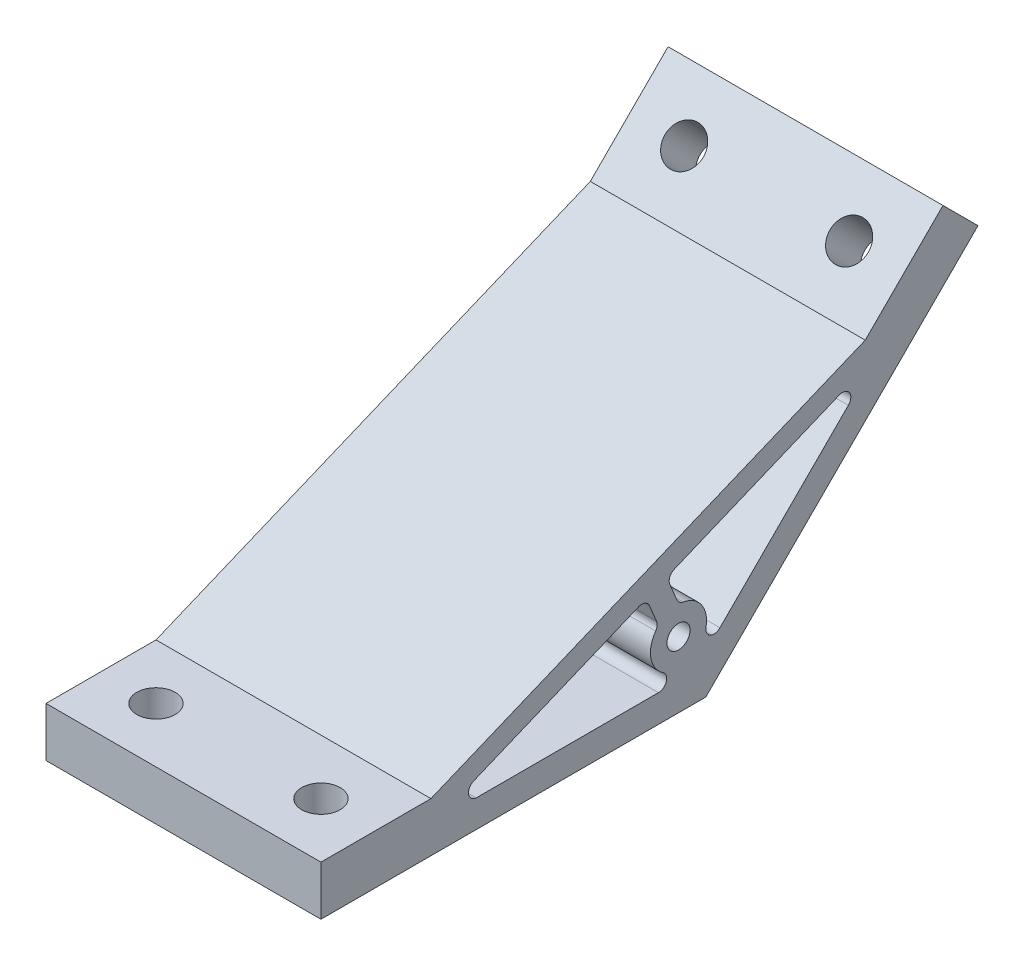
SolidWorks part; units mm, degrees
ref_plane "Front Plane" through (0, 0, 0) normal (0, 0, 1) x (1, 0, 0)
ref_plane "Top Plane" through (0, 0, 0) normal (0, 1, 0) x (1, 0, 0)
ref_plane "Right Plane" through (0, 0, 0) normal (1, 0, 0) x (0, 0, -1)
ref_plane "Plane1" through (0, 0, 0) normal (1, 0, 0) x (0, 0, -1)
sketch "Sketch1" plane through (0, 0, 0) normal (1, 0, 0) x (0, 0, -1)
  line L0 (-70, 0) -> (0, 0)
  line L1 (0, 0) -> (49.4975, 49.4975)
  line L2 (49.4975, 49.4975) -> (43.1335, 55.8614)
  line L3 (43.1335, 55.8614) -> (28.9914, 41.7193)
  line L4 (28.9914, 41.7193) -> (-49.9914, 9)
  line L5 (-49.9914, 9) -> (-70, 9)
  line L6 (-70, 9) -> (-70, 0)
  line L7 (-6.5518, 21.0437) -> (-5.2641, 17.935)
  line L8 (2.5589, 9.63) -> (25.9249, 32.996)
  line L9 (24.2902, 35.4424) -> (-5.74, 23.0035)
  line L10 (-41.7559, 5.0029) -> (-8.619, 5)
  line L11 (-8.9596, 16.4042) -> (-10.2473, 19.5129)
  line L12 (-12.1145, 20.3596) -> (-42.2372, 7.8859)
  arc A0 (-5.74, 23.0035) -> (-6.5518, 21.0437) centre (-5.166, 21.6177) ccw
  arc A1 (-5.2641, 17.935) -> (-4.1265, 17.0297) centre (-3.8783, 18.509) ccw
  arc A2 (-4.1265, 17.0297) -> (0.0281, 10.9882) centre (-4.9706, 12) cw
  arc A3 (0.0281, 10.9882) -> (2.5589, 9.63) centre (1.4983, 10.6906) ccw
  arc A4 (25.9249, 32.996) -> (24.2902, 35.4424) centre (24.8642, 34.0566) ccw
  circle A5 centre (-4.9706, 12) radius 2.1
  arc A6 (-42.2372, 7.8859) -> (-41.7559, 5.0029) centre (-41.6633, 6.5) ccw
  arc A7 (-8.619, 5) -> (-7.7993, 7.7564) centre (-8.6188, 6.5) ccw
  arc A8 (-7.7993, 7.7564) -> (-9.1239, 14.9597) centre (-4.9706, 12) cw
  arc A9 (-9.1239, 14.9597) -> (-8.9596, 16.4042) centre (-10.3455, 15.8302) ccw
  arc A10 (-10.2473, 19.5129) -> (-12.1145, 20.3596) centre (-11.6331, 18.9389) ccw
extrude "Boss-Extrude1" add sketch "Sketch1" against normal blind 25 and the other way blind 25
ref_plane "Plane2" through (0, 0, 0) normal (0, 1, 0) x (1, 0, 0)
sketch "Sketch2" plane through (0, 0, 0) normal (0, 1, 0) x (1, 0, 0)
  circle A0 centre (-15, -60) radius 3.5
extrude "Cut-Extrude1" cut sketch "Sketch2" along normal blind 9
ref_plane "Plane3" through (0, 0, 0) normal (0, 1, 0) x (1, 0, 0)
sketch "Sketch3" plane through (0, 0, 0) normal (0, 1, 0) x (1, 0, 0)
  circle A0 centre (15, -60) radius 3.5
extrude "Cut-Extrude2" cut sketch "Sketch3" along normal blind 9
ref_plane "Plane4" through (15, 0, 0) normal (1, 0, 0) x (0, 0, -1)
sketch "Sketch4" plane through (15, 0, 0) normal (1, 0, 0) x (0, 0, -1)
  line L0 (36.0624, 48.7904) -> (38.5373, 51.2652)
  line L1 (38.5373, 51.2652) -> (44.9013, 44.9013)
  line L2 (44.9013, 44.9013) -> (42.4264, 42.4264)
  line L3 (42.4264, 42.4264) -> (36.0624, 48.7904)
  line L4 (42.4264, 42.4264) -> (36.0624, 48.7904) construction
revolve "Cut-Revolve1" cut sketch "Sketch4" angle 360 about L4 reverse direction yes
ref_plane "Plane5" through (-15, 0, 0) normal (1, 0, 0) x (0, 0, -1)
sketch "Sketch5" plane through (-15, 0, 0) normal (1, 0, 0) x (0, 0, -1)
  line L0 (36.0624, 48.7904) -> (38.5373, 51.2652)
  line L1 (38.5373, 51.2652) -> (44.9013, 44.9013)
  line L2 (44.9013, 44.9013) -> (42.4264, 42.4264)
  line L3 (42.4264, 42.4264) -> (36.0624, 48.7904)
  line L4 (42.4264, 42.4264) -> (36.0624, 48.7904) construction
revolve "Cut-Revolve2" cut sketch "Sketch5" angle 360 about L4 reverse direction yes
